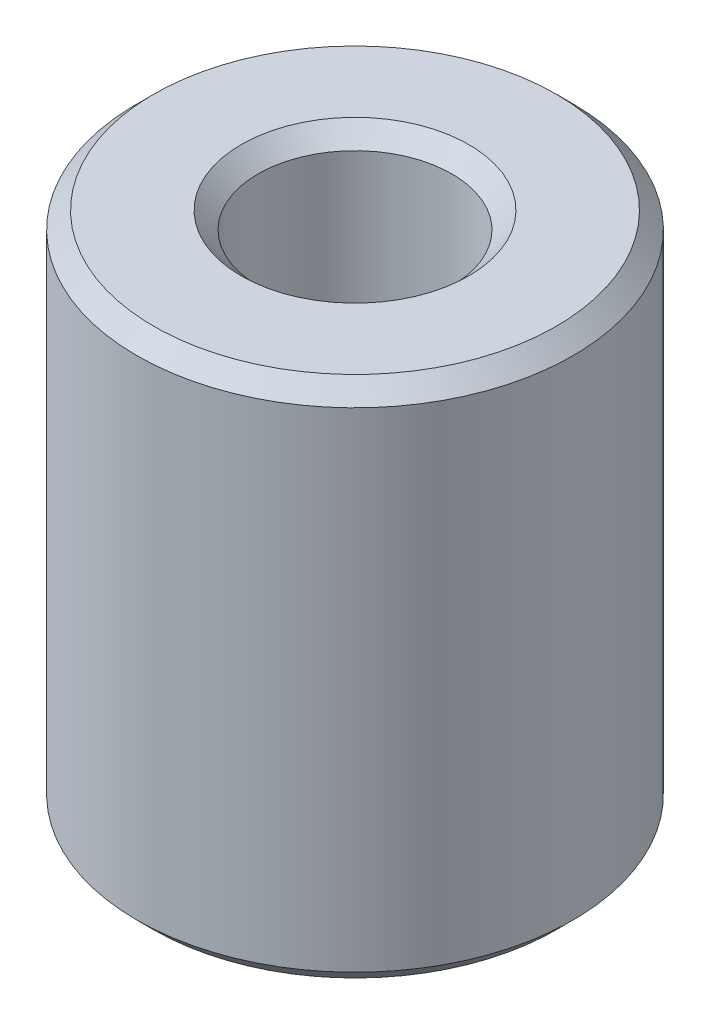
SolidWorks part; units mm, degrees
ref_plane "Front Plane" through (0, 0, 0) normal (0, 0, 1) x (1, 0, 0)
ref_plane "Top Plane" through (0, 0, 0) normal (0, 1, 0) x (1, 0, 0)
ref_plane "Right Plane" through (0, 0, 0) normal (1, 0, 0) x (0, 0, -1)
sketch "Sketch1" plane through (0, 0, 0) normal (0, 1, 0) x (1, 0, 0)
  circle A0 centre (0, 0) radius 10
  dimension "SLEEVE_OD" = 20
extrude "Boss-Extrude1" add sketch "Sketch1" along normal blind 23.9673
sketch "Sketch2" plane through (0, 0, 0) normal (0, 1, 0) x (1, 0, 0)
  circle A0 centre (0, 0) radius 4.4429
  dimension "BORE_D" = 8.8858
extrude "Cut-Extrude1" cut sketch "Sketch2" along normal through all
chamfer "Chamfer1" distance 0.7759 angle 45 4 edges at (0, 23.9673, 4.4429) (0, 0, 4.4429) (0, 0, 10) (0, 23.9673, 10)
